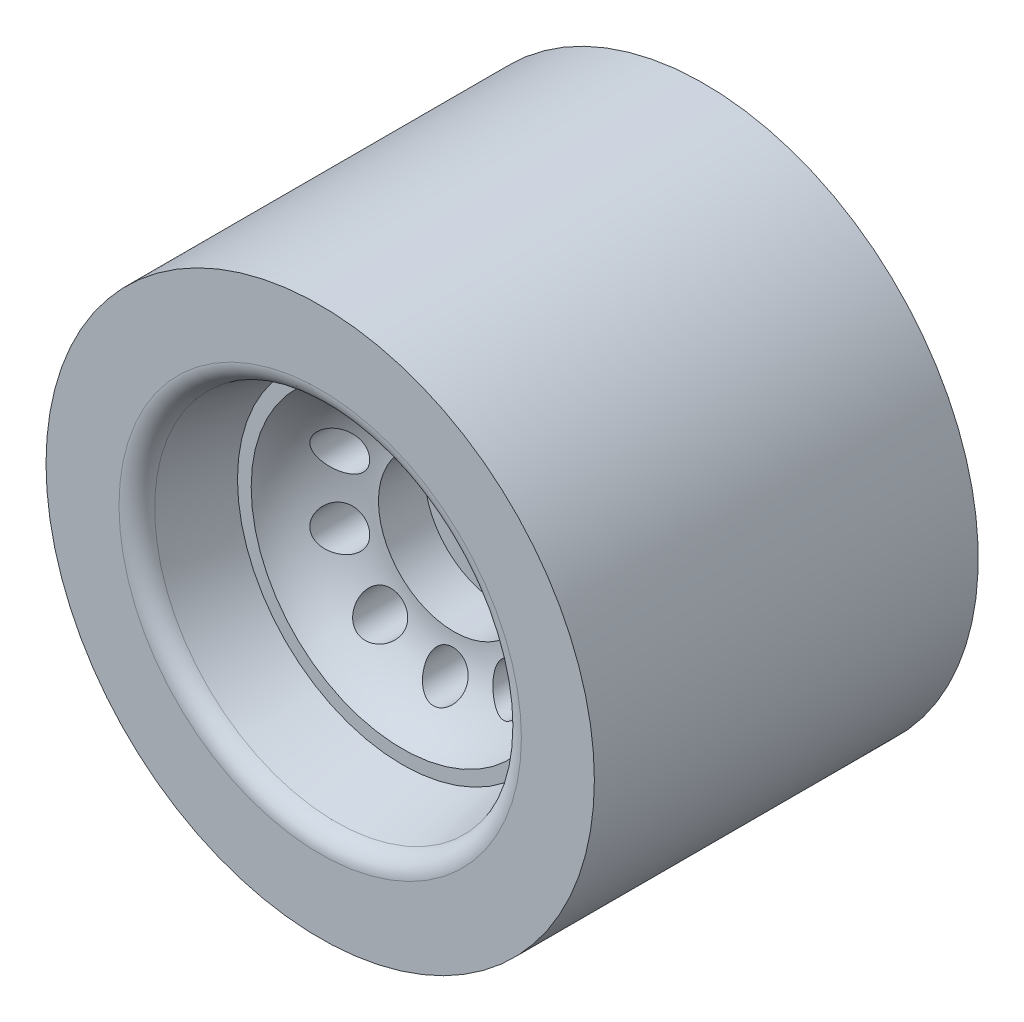
SolidWorks part; units mm, degrees
material "폴리우레탄(11671)"
ref_plane "정면" through (0, 0, 0) normal (0, 0, 1) x (1, 0, 0)
ref_plane "윗면" through (0, 0, 0) normal (0, 1, 0) x (1, 0, 0)
ref_plane "우측면" through (0, 0, 0) normal (1, 0, 0) x (0, 0, -1)
sketch "스케치1" plane through (0, 0, 0) normal (0, 0, 1) x (1, 0, 0)
  circle A0 centre (0, 0) radius 40
  dimension "D1" = 80
extrude "보스-돌출1" add sketch "스케치1" along normal mid plane 56
sketch "스케치2" plane through (0, 0, 28) normal (0, 0, 1) x (1, 0, 0)
  circle A0 centre (0, 0) radius 8.5
  dimension "D1" = 17
extrude "컷-돌출1" cut sketch "스케치2" against normal through all
sketch "스케치4" plane through (0, 0, 0) normal (1, 0, 0) x (0, 0, -1)
  line L0 (28, 0) -> (-28, 0) construction
  line L1 (28, -40) -> (28, 40) construction
  line L2 (-28, 40) -> (-28, -40) construction
  line L3 (0, 0) -> (0, -40) construction
  line L4 (-28, -40) -> (28, -40) construction
  line L5 (28, 40) -> (26.6, 33.9)
  line L7 (15.1, 0) -> (28, 0)
  line L8 (15.1, 0) -> (15.1, 11)
  line L9 (26.6, 33.9) -> (25.6, 33.4)
  line L10 (28, 0) -> (28, 40)
  line L11 (-28, 0) -> (-28, 27)
  line L12 (-28, 27) -> (-16.0084, 24.06)
  line L13 (-8.5, 11) -> (-8.5, 0)
  line L14 (-8.5, 0) -> (-28, 0)
  line L15 (-16.0084, 24.06) -> (-16.0084, 22.06)
  arc A0 (22.6084, 22.06) -> (24.2058, 28.6555) centre (43.7359, 20.4341) cw
  arc A1 (15.1, 11) -> (22.6084, 22.06) centre (27, 11) cw
  arc A2 (24.2058, 28.6555) -> (25.6, 33.4) centre (3.9291, 37.191) ccw
  arc A3 (-16.0084, 22.06) -> (-8.5, 11) centre (-20.4, 11) cw
  dimension "D5" = 11.9
  dimension "D4" = 0.5
  dimension "D9" = 21.19
  dimension "D12" = 22
  dimension "D14" = 13
  dimension "D13" = 11.9
  dimension "D2" = 22.06
  dimension "D3" = 6.1
  dimension "D6" = 11
  dimension "D7" = 11.5
  dimension "D8" = 1
  dimension "D15" = 19.5
  dimension "D16" = 2
  dimension "D17" = 1.4
  dimension "D18" = 11.3445
revolve "컷-회전1" cut sketch "스케치4" angle 360 about L0
sketch "스케치5" plane through (0, 0, 0) normal (0, 0, 1) x (1, 0, 0)
  line L0 (0, 0) -> (0, 40) construction
  circle A0 centre (0, 0) radius 40 construction
  circle A1 centre (0, 15.875) radius 3
  dimension "D1" = 6
  dimension "D2" = 15.875
extrude "컷-돌출2" cut sketch "스케치5" against normal through all both and the other way through all
pattern_circular "원형 패턴1" count 10 over 360 about axis through (0, 0, -28) along (0, 0, 1) of "컷-돌출2"
fillet "필렛1" radius 3 1 edges at (-27, 0, 28)
sketch "스케치6" plane through (0, 0, 8.5) normal (0, 0, 1) x (1, 0, 0)
  circle A0 centre (0, 0) radius 11
  dimension "D1" = 22
extrude "컷-돌출3" cut sketch "스케치6" against normal blind 6.75
sketch "스케치7" plane through (0, 0, -15.1) normal (0, 0, -1) x (-1, 0, 0)
  circle A0 centre (0, 0) radius 11
  dimension "D1" = 22
extrude "컷-돌출4" cut sketch "스케치7" against normal blind 6.75
